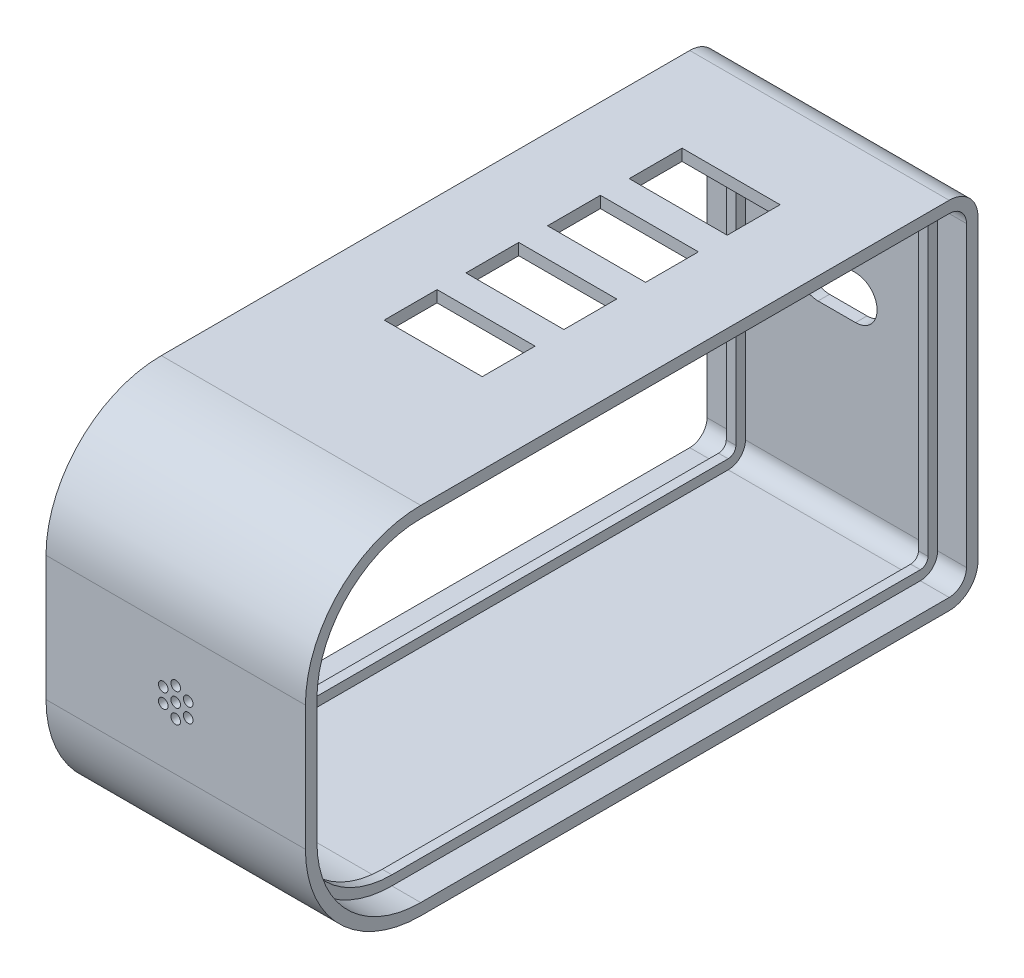
SolidWorks part; units mm, degrees
material "ABS"
ref_plane "Front Plane" through (0, 0, 0) normal (0, 0, 1) x (1, 0, 0)
ref_plane "Top Plane" through (0, 0, 0) normal (0, 1, 0) x (1, 0, 0)
ref_plane "Right Plane" through (0, 0, 0) normal (1, 0, 0) x (0, 0, -1)
sketch "Sketch1" plane through (0, 0, 0) normal (1, 0, 0) x (0, 0, -1)
  line L1 (-23, -18.5) -> (32, -18.5)
  line L2 (-35, -6.5) -> (-35, 6.5)
  line L3 (-23, 18.5) -> (32, 18.5)
  line L4 (35, -15.5) -> (35, 15.5)
  line L5 (-35, -18.5) -> (35, 18.5) construction
  line L6 (-35, 18.5) -> (35, -18.5) construction
  arc A0 (32, -18.5) -> (35, -15.5) centre (32, -15.5) ccw
  arc A1 (32, 18.5) -> (35, 15.5) centre (32, 15.5) cw
  arc A2 (-23, -18.5) -> (-35, -6.5) centre (-23, -6.5) cw
  arc A3 (-35, 6.5) -> (-23, 18.5) centre (-23, 6.5) cw
  point P0 (0, 0)
  dimension "D3" = 3
  dimension "D4" = 12
  dimension "D1" = 70
  dimension "D2" = 37
extrude "Boss-Extrude1" add sketch "Sketch1" along normal mid plane 27
sketch "Sketch2" plane through (-13.5, 0, 0) normal (-1, 0, 0) x (0, 0, 1)
  line L8 (-33.8, 15.5) -> (-33.8, -15.5)
  line L9 (-32, -17.3) -> (23, -17.3)
  line L10 (33.8, -6.5) -> (33.8, 6.5)
  line L11 (23, 17.3) -> (-32, 17.3)
  line L12 (-33.8, 15.5) -> (-33.8, -15.5)
  line L13 (-32, -17.3) -> (23, -17.3)
  line L14 (33.8, -6.5) -> (33.8, 6.5)
  line L15 (23, 17.3) -> (-32, 17.3)
  arc A2 (-32, 17.3) -> (-33.8, 15.5) centre (-32, 15.5) ccw
  arc A3 (-32, 17.3) -> (-33.8, 15.5) centre (-32, 15.5) ccw
  arc A4 (-33.8, -15.5) -> (-32, -17.3) centre (-32, -15.5) ccw
  arc A5 (-33.8, -15.5) -> (-32, -17.3) centre (-32, -15.5) ccw
  arc A8 (23, -17.3) -> (33.8, -6.5) centre (23, -6.5) ccw
  arc A9 (23, -17.3) -> (33.8, -6.5) centre (23, -6.5) ccw
  arc A10 (33.8, 6.5) -> (23, 17.3) centre (23, 6.5) ccw
  arc A11 (33.8, 6.5) -> (23, 17.3) centre (23, 6.5) ccw
  dimension "D1" = 1.2
extrude "Cut-Extrude1" cut sketch "Sketch2" against normal up to surface (27 mm away) up to face at (13.5, 0, -1.784)
sketch "Sketch3" plane through (0, 18.5, 0) normal (0, 1, 0) x (1, 0, 0)
  line L0 (0, -35) -> (0, 35) construction
  line L1 (13.5, -35) -> (-13.5, -35) construction
  line L2 (13.5, 35) -> (-13.5, 35) construction
  line L3 (5.1, 17.3) -> (-5.1, 17.3)
  line L4 (5.1, 17.3) -> (5.1, 22.8)
  line L5 (-5.1, 17.3) -> (-5.1, 22.8)
  line L6 (5.1, 22.8) -> (-5.1, 22.8)
  line L7 (5.1, 17.3) -> (-5.1, 22.8) construction
  line L8 (-5.1, 17.3) -> (5.1, 22.8) construction
  line L9 (13.5, 33.8) -> (-13.5, 33.8) construction
  line L10 (5.1, 8.8) -> (-5.1, 8.8)
  line L11 (5.1, 8.8) -> (5.1, 14.3)
  line L12 (5.1, 14.3) -> (-5.1, 14.3)
  line L13 (-5.1, 8.8) -> (-5.1, 14.3)
  line L14 (0, -43.5) -> (0, 26.5) construction
  line L15 (5.1, 0.3) -> (-5.1, 0.3)
  line L16 (5.1, 0.3) -> (5.1, 5.8)
  line L17 (5.1, 5.8) -> (-5.1, 5.8)
  line L18 (-5.1, 0.3) -> (-5.1, 5.8)
  line L19 (0, -52) -> (0, 18) construction
  line L20 (5.1, -8.2) -> (-5.1, -8.2)
  line L21 (5.1, -8.2) -> (5.1, -2.7)
  line L22 (5.1, -2.7) -> (-5.1, -2.7)
  line L23 (-5.1, -8.2) -> (-5.1, -2.7)
  line L24 (0, -60.5) -> (0, 9.5) construction
  point P7 (0, 20.05)
  dimension "D1" = 5.5
  dimension "D2" = 11
  dimension "D3" = 10.2
  dimension "D5" = 3
  dimension "D4" = 4
extrude "Cut-Extrude2" cut sketch "Sketch3" against normal up to surface (1.2 mm away) up to face at (0, 17.3, -4.5)
sketch "Sketch4" plane through (0, 0, -35) normal (0, 0, -1) x (-1, 0, 0)
  line L0 (0, 18.5) -> (0, -18.5) construction
  line L1 (-13.5, 18.5) -> (13.5, 18.5) construction
  line L2 (-13.5, -18.5) -> (13.5, -18.5) construction
  line L3 (-4.2, 14.3) -> (4.2, 14.3)
  line L4 (-4.2, 14.3) -> (-4.2, 9.3)
  line L5 (4.2, 14.3) -> (4.2, 9.3)
  line L6 (-4.2, 9.3) -> (4.2, 9.3)
  line L7 (-4.2, 14.3) -> (4.2, 9.3) construction
  line L8 (4.2, 14.3) -> (-4.2, 9.3) construction
  line L9 (-1.95, 5.3) -> (1.95, 5.3)
  line L12 (-1.95, 0.8) -> (1.95, 0.8)
  line L13 (-1.95, 5.3) -> (1.95, 0.8) construction
  line L14 (1.95, 5.3) -> (-1.95, 0.8) construction
  line L15 (-13.5, 17.3) -> (13.5, 17.3) construction
  arc A0 (1.95, 5.3) -> (1.95, 0.8) centre (1.95, 3.05) cw
  arc A1 (-1.95, 5.3) -> (-1.95, 0.8) centre (-1.95, 3.05) ccw
  point P7 (0, 11.8)
  point P8 (0, 3.05)
  point P20 (-4.2, 3.05)
  point P21 (4.2, 3.05)
  point P22 (0, 0)
  dimension "D1" = 5
  dimension "D2" = 3
  dimension "D3" = 8.4
  dimension "D4" = 8.4
  dimension "D5" = 4.5
  dimension "D6" = 12
extrude "Cut-Extrude3" cut sketch "Sketch4" against normal up to surface (1.2 mm away) up to face at (0, 0, -33.8)
sketch "Sketch5" plane through (0, 0, 35) normal (0, 0, 1) x (1, 0, 0)
  circle A0 centre (0, 0) radius 0.5
  point P5 (0, 0)
  dimension "D2" = 1
extrude "Cut-Extrude4" cut sketch "Sketch5" against normal up to surface (1.2 mm away) up to face at (0, 0, 33.8)
sketch "Sketch6" plane through (0, 0, 35) normal (0, 0, 1) x (1, 0, 0)
  circle A0 centre (0, 1.5) radius 0.5
  circle A1 centre (0, 0) radius 0.5 construction
  circle A2 centre (1.299, 0.75) radius 0.5
  circle A3 centre (1.299, -0.75) radius 0.5
  circle A4 centre (0, -1.5) radius 0.5
  circle A5 centre (-1.299, -0.75) radius 0.5
  circle A6 centre (-1.299, 0.75) radius 0.5
  point P5 (0, 0)
  point P18 (0, 0)
  dimension "D1" = 1.5
  dimension "D2" = 6
extrude "Cut-Extrude6" cut sketch "Sketch6" against normal up to surface (1.2 mm away) up to face at (0.5, 0, 33.8)
sketch "Sketch7" plane through (0, 0, 33.8) normal (0, 0, -1) x (-1, 0, 0)
  line L0 (0, 2.9453) -> (0, -3.3771) construction
  line L1 (0.0987, 0.5) -> (5.4522, 0.5) construction
  circle A0 centre (0, 0) radius 0.5 construction
  circle A1 centre (-5.75, -0.75) radius 1.25 construction
  circle A2 centre (5.75, -0.75) radius 1.25 construction
  circle A3 centre (-5.75, -0.75) radius 1.75
  circle A4 centre (5.75, -0.75) radius 1.75
  point P2 (0, 0.5)
  point P8 (-7, -0.75)
  dimension "D1" = 2.5
  dimension "D2" = 7
  dimension "D3" = 0.5
  dimension "D4" = 0.5
extrude "Boss-Extrude2" add sketch "Sketch7" along normal blind 2.5
sketch "Sketch8" plane through (0, 0, 31.3) normal (0, 0, -1) x (-1, 0, 0)
  circle A2 centre (-5.75, -0.75) radius 0.75
  circle A3 centre (-5.75, -0.75) radius 0.75
  circle A5 centre (5.75, -0.75) radius 0.75
  circle A6 centre (5.75, -0.75) radius 0.75
  dimension "D1" = 1
  dimension "D2" = 1
extrude "Cut-Extrude7" cut sketch "Sketch8" against normal blind 3
ref_plane "Plane5" through (10.5, 0, 0) normal (1, 0, 0) x (0, 0, -1)
sketch "Sketch9" plane through (10.5, 0, 0) normal (1, 0, 0) x (0, 0, -1)
  line L0 (-33.8, -6.5) -> (-33.8, 6.5) construction
  line L1 (-23, 17.3) -> (32, 17.3) construction
  line L2 (33.8, 15.5) -> (33.8, -15.5) construction
  line L3 (32, -17.3) -> (-23, -17.3) construction
  line L4 (-33.8, -6.5) -> (-33.8, 6.5)
  line L5 (-23, 17.3) -> (32, 17.3)
  line L6 (33.8, 15.5) -> (33.8, -15.5)
  line L7 (32, -17.3) -> (-23, -17.3)
  line L8 (-32.8, -6.5) -> (-32.8, 6.5)
  line L9 (-23, 16.3) -> (32, 16.3)
  line L10 (32.8, 15.5) -> (32.8, -15.5)
  line L11 (32, -16.3) -> (-23, -16.3)
  arc A0 (-23, 17.3) -> (-33.8, 6.5) centre (-23, 6.5) ccw construction
  arc A1 (33.8, 15.5) -> (32, 17.3) centre (32, 15.5) ccw construction
  arc A2 (32, -17.3) -> (33.8, -15.5) centre (32, -15.5) ccw construction
  arc A3 (-33.8, -6.5) -> (-23, -17.3) centre (-23, -6.5) ccw construction
  arc A4 (-23, 17.3) -> (-33.8, 6.5) centre (-23, 6.5) ccw
  arc A5 (33.8, 15.5) -> (32, 17.3) centre (32, 15.5) ccw
  arc A6 (32, -17.3) -> (33.8, -15.5) centre (32, -15.5) ccw
  arc A7 (-33.8, -6.5) -> (-23, -17.3) centre (-23, -6.5) ccw
  arc A8 (-23, 16.3) -> (-32.8, 6.5) centre (-23, 6.5) ccw
  arc A9 (32.8, 15.5) -> (32, 16.3) centre (32, 15.5) ccw
  arc A10 (32, -16.3) -> (32.8, -15.5) centre (32, -15.5) ccw
  arc A11 (-32.8, -6.5) -> (-23, -16.3) centre (-23, -6.5) ccw
  dimension "D1" = 1
extrude "Boss-Extrude3" add sketch "Sketch9" against normal blind 1
mirror "Mirror1" about plane through (0, 0, 0) normal (1, 0, 0) of "Boss-Extrude3"
